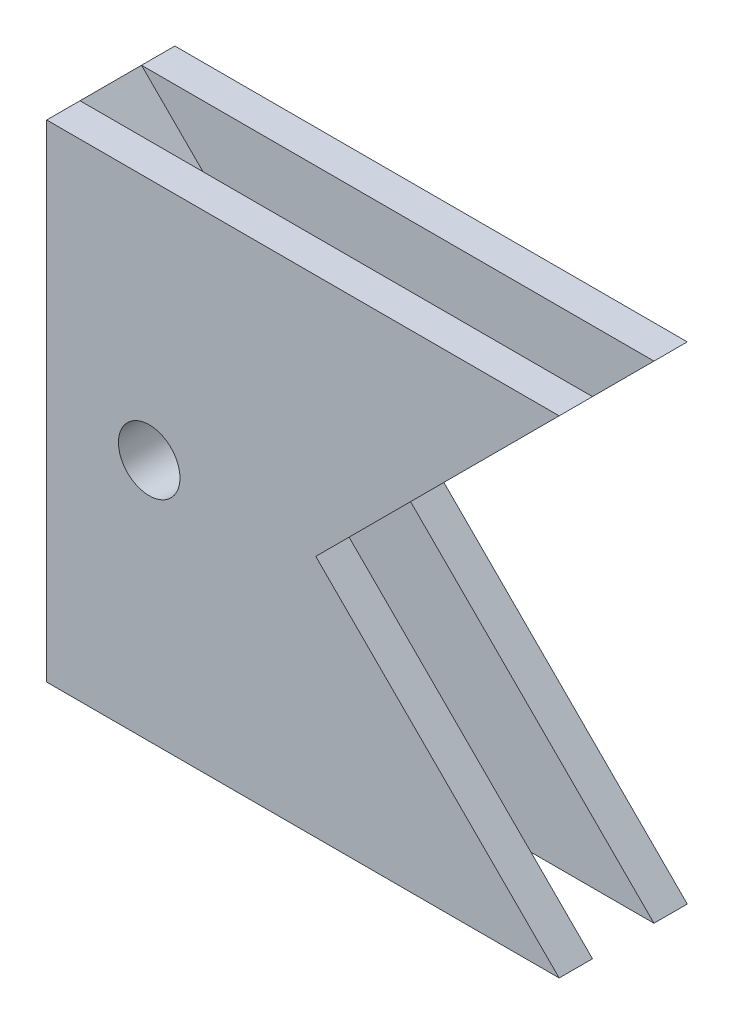
SolidWorks part; units mm, degrees
ref_plane "Front Plane" through (0, 0, 0) normal (0, 0, 1) x (1, 0, 0)
ref_plane "Top Plane" through (0, 0, 0) normal (0, 1, 0) x (1, 0, 0)
ref_plane "Right Plane" through (0, 0, 0) normal (1, 0, 0) x (0, 0, -1)
sketch "Sketch1" plane through (0, 0, 0) normal (0, 0, 1) x (1, 0, 0)
  line L0 (100, 95) -> (52.5, 47.5)
  line L1 (0, 0) -> (100, 0)
  line L2 (0, 0) -> (0, 95)
  line L3 (0, 95) -> (100, 95)
  line L5 (52.5, 47.5) -> (100, 0)
  line L6 (0, 95) -> (43.9645, 51.0355)
  line L7 (43.9645, 43.9645) -> (0, 0)
  circle A0 centre (20, 47.5) radius 6
  arc A1 (43.9645, 51.0355) -> (43.9645, 43.9645) centre (40.4289, 47.5) cw
  point P4 (0, 0)
  point P10 (-0.1866, 30.6942)
  point P13 (47.5, 47.5)
  point P14 (52.4884, 47.5)
  point P15 (0, 0)
  dimension "D1" = 12
  dimension "D5" = 5
  dimension "D2" = 95
  dimension "D3" = 100
  dimension "D4" = 20
extrude "Boss-Extrude1" add sketch "Sketch1" along normal blind 6.5 from offset 12.5 contours L6 A1 L7 L1 L5 L0 L3 region at (49.9956, 47.5, 0) offset against normal yes
extrude "Boss-Extrude2" add sketch "Sketch1<3>" along normal mid plane 25 contours A1 L6 L2 L7 A0 region at (21.2376, 72.2732, 0)
sketch "Sketch1<3>" plane through (0, 0, 0) normal (0, 0, 1) x (1, 0, 0) same geometry as "Sketch1"
mirror "Mirror2" about plane through (0, 0, 0) normal (0, 0, 1) of "Boss-Extrude1"
